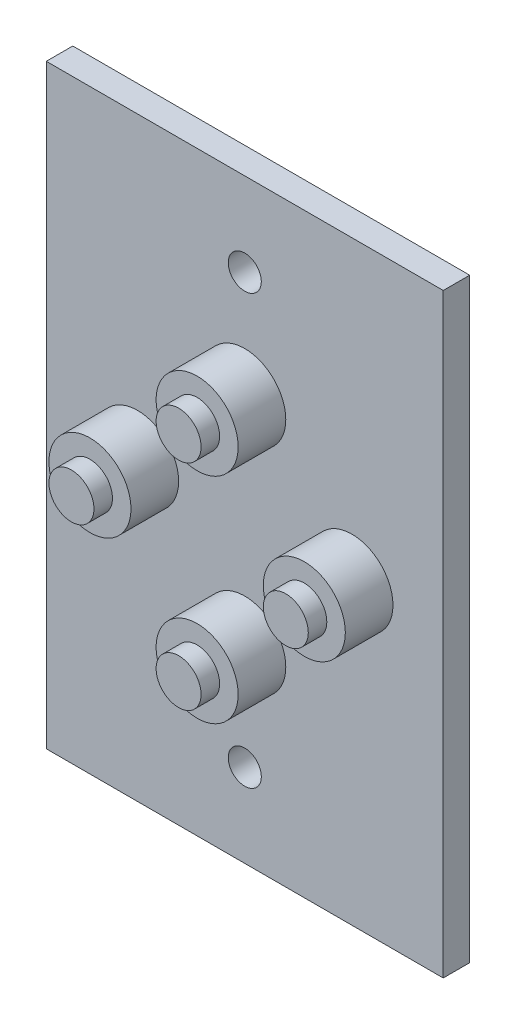
SolidWorks part; units mm, degrees
ref_plane "Front Plane" through (0, 0, 0) normal (0, 0, 1) x (1, 0, 0)
ref_plane "Top Plane" through (0, 0, 0) normal (0, 1, 0) x (1, 0, 0)
ref_plane "Right Plane" through (0, 0, 0) normal (1, 0, 0) x (0, 0, -1)
sketch "Sketch1" plane through (0, 0, 0) normal (0, 0, 1) x (1, 0, 0)
  line L1 (-15, 22.5) -> (15, 22.5)
  line L2 (-15, 22.5) -> (-15, -22.5)
  line L3 (-15, -22.5) -> (15, -22.5)
  line L4 (15, 22.5) -> (15, -22.5)
  line L5 (-15, 22.5) -> (15, -22.5) construction
  line L6 (-15, -22.5) -> (15, 22.5) construction
  point P0 (0, 0)
  dimension "D1" = 45
  dimension "D2" = 30
extrude "Boss-Extrude1" add sketch "Sketch1" along normal blind 2
sketch "Sketch2" plane through (0, 0, 2) normal (0, 0, 1) x (1, 0, 0)
  line L0 (-15, -22.5) -> (15, -22.5) construction
  line L1 (15, 22.5) -> (-15, 22.5) construction
  line L2 (15, -22.5) -> (15, 22.5) construction
  line L3 (-15, 22.5) -> (-15, -22.5) construction
  circle A0 centre (-8.1, 0) radius 3.1
  circle A1 centre (8.1, 0) radius 3.1
  circle A2 centre (0, 8.1) radius 3.1
  circle A3 centre (0, -8.1) radius 3.1
  dimension "D1" = 6.2
  dimension "D2" = 8.1
  dimension "D3" = 6.2
  dimension "D4" = 8.1
  dimension "D5" = 6.2
  dimension "D6" = 6.2
  dimension "D8" = 8.1
  dimension "D9" = 14.4
  dimension "D10" = 14.4
  dimension "D11" = 6.9
  dimension "D12" = 6.9
  dimension "D7" = 8.1
extrude "Boss-Extrude2" add sketch "Sketch2" along normal blind 3.6
sketch "Sketch3" plane through (0, 0, 5.6) normal (0, 0, 1) x (1, 0, 0)
  circle A0 centre (0, 8.1) radius 1.7
  dimension "D1" = 3.4
extrude "Boss-Extrude3" add sketch "Sketch3" along normal blind 1.4
sketch "Sketch4" plane through (0, 0, 5.6) normal (0, 0, 1) x (1, 0, 0)
  circle A0 centre (-8.1, 0) radius 1.7
  dimension "D1" = 3.4
extrude "Boss-Extrude4" add sketch "Sketch4" along normal blind 1.4
sketch "Sketch5" plane through (0, 0, 5.6) normal (0, 0, 1) x (1, 0, 0)
  circle A0 centre (8.1, 0) radius 1.7
  dimension "D1" = 3.4
extrude "Boss-Extrude5" add sketch "Sketch5" along normal blind 1.4
sketch "Sketch6" plane through (0, 0, 5.6) normal (0, 0, 1) x (1, 0, 0)
  circle A0 centre (0, -8.1) radius 1.7
  dimension "D1" = 3.4
extrude "Boss-Extrude6" add sketch "Sketch6" along normal blind 1.4
sketch "Sketch7" plane through (0, 0, 2) normal (0, 0, 1) x (1, 0, 0)
  circle A0 centre (0, 16.2) radius 1.25
  circle A1 centre (0, -16.2) radius 1.25
  circle A2 centre (0, 8.1) radius 1.7 construction
  circle A3 centre (0, -8.1) radius 1.7 construction
  dimension "D1" = 2.5
  dimension "D2" = 2.5
  dimension "D3" = 8.1
  dimension "D4" = 8.1
extrude "Cut-Extrude1" cut sketch "Sketch7" against normal blind 3
